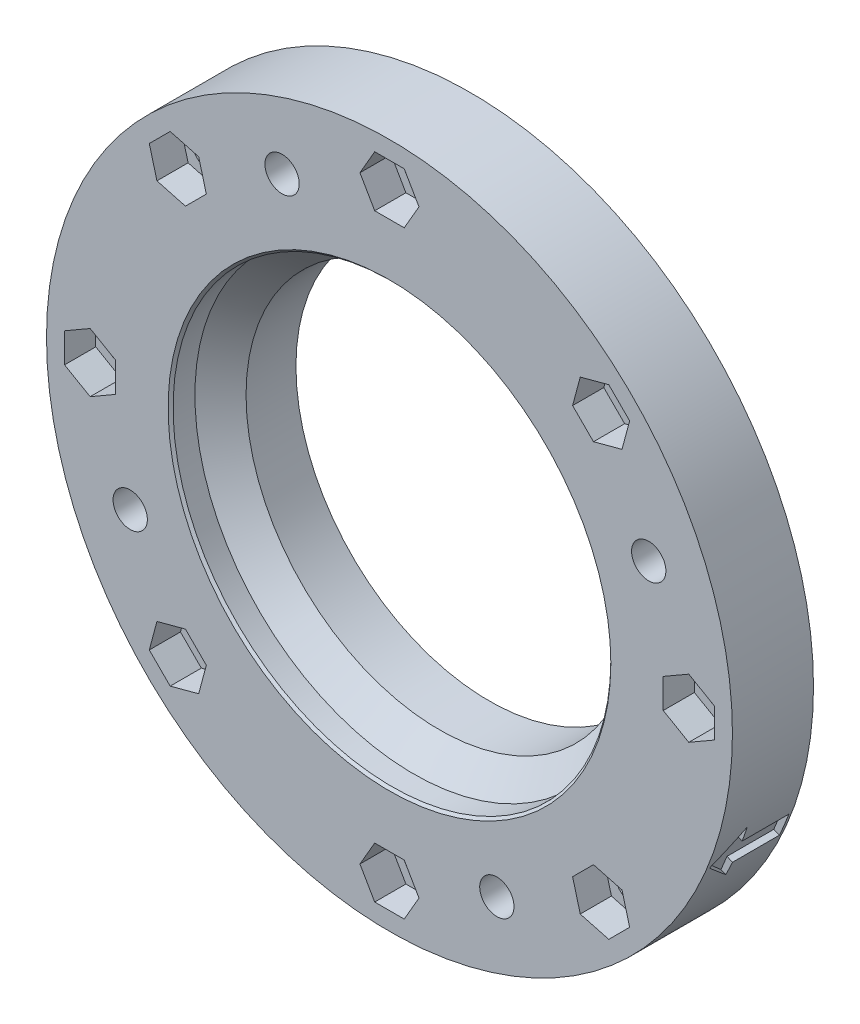
SolidWorks part; units mm, degrees
ref_plane "Piano frontale" through (0, 0, 0) normal (0, 0, 1) x (1, 0, 0)
ref_plane "Piano superiore" through (0, 0, 0) normal (0, 1, 0) x (1, 0, 0)
ref_plane "Piano destro" through (0, 0, 0) normal (1, 0, 0) x (0, 0, -1)
sketch "Schizzo1" plane through (0, 0, 0) normal (0, 0, 1) x (1, 0, 0)
  circle A0 centre (0, 0) radius 34
  circle A1 centre (0, 0) radius 55
  dimension "D1" = 110
  dimension "D2" = 68
extrude "Estrusione-Estrusione1" add sketch "Schizzo1" along normal blind 13
sketch "Schizzo2" plane through (0, 0, 13) normal (0, 0, 1) x (1, 0, 0)
  circle A0 centre (0, 0) radius 34
  circle A2 centre (0, 0) radius 34 construction
extrude "Estrusione-Estrusione2" add sketch "Schizzo2" against normal blind 8
sketch "Schizzo3" plane through (0, 0, 13) normal (0, 0, 1) x (1, 0, 0)
  circle A0 centre (0, 0) radius 48 construction
  circle A1 centre (0, 48) radius 2.75
  dimension "D1" = 96
  dimension "D2" = 5.5
extrude "Taglio-Estrusione1" cut sketch "Schizzo3" against normal through all
pattern_circular "RipetizioneCircolare1" count 8 over 360 about axis through (0, 0, 13) along (0, 0, -1) of "Taglio-Estrusione1"
sketch "Schizzo6" plane through (0, 0, 13) normal (0, 0, 1) x (1, 0, 0)
  line L1 (4.7343, 48) -> (2.3671, 52.1)
  line L2 (2.3671, 52.1) -> (-2.3671, 52.1)
  line L3 (-2.3671, 52.1) -> (-4.7343, 48)
  line L4 (-4.7343, 48) -> (-2.3671, 43.9)
  line L5 (-2.3671, 43.9) -> (2.3671, 43.9)
  line L6 (2.3671, 43.9) -> (4.7343, 48)
  circle A0 centre (0, 48) radius 4.1 construction
  dimension "D1" = 8.2
extrude "Taglio-Estrusione3" cut sketch "Schizzo6" against normal blind 5
pattern_circular "RipetizioneCircolare2" count 8 over 360 about axis through (0, 0, 13) along (0, 0, -1) of "Taglio-Estrusione3"
sketch "Schizzo7" plane through (0, 0, 13) normal (0, 0, 1) x (1, 0, 0)
  circle A0 centre (0, 0) radius 35
  dimension "D1" = 70
extrude "Taglio-Estrusione4" cut sketch "Schizzo7" against normal blind 8
sketch "Schizzo8" plane through (0, 0, 13) normal (0, 0, 1) x (1, 0, 0)
  line L0 (0, 48) -> (0, -43.9) construction
  line L1 (41.5746, 17.2208) -> (17.2208, -41.5746) construction
  line L2 (41.5746, 17.2208) -> (-17.2208, 41.5746) construction
  line L3 (-17.2208, 41.5746) -> (-41.5746, -17.2208) construction
  line L4 (17.2208, -41.5746) -> (-41.5746, -17.2208) construction
  line L5 (41.5746, 17.2208) -> (-41.5746, -17.2208) construction
  line L6 (-17.2208, 41.5746) -> (17.2208, -41.5746) construction
  line L7 (2.3671, -43.9) -> (-2.3671, -43.9) construction
  circle A0 centre (0, 0) radius 45 construction
  circle A1 centre (-17.2208, 41.5746) radius 2.75
  circle A2 centre (41.5746, 17.2208) radius 2.75
  circle A3 centre (17.2208, -41.5746) radius 2.75
  circle A4 centre (-41.5746, -17.2208) radius 2.75
  dimension "D1" = 90
  dimension "D3" = 5.5
  dimension "D2" = 22.5
extrude "Taglio-Estrusione5" cut sketch "Schizzo8" against normal through all
sketch "Schizzo9" plane through (0, 0, 0) normal (0, 0, -1) x (-1, 0, 0)
  line L1 (19.5879, 45.6746) -> (14.8536, 45.6746)
  line L2 (14.8536, 45.6746) -> (12.4865, 41.5746)
  line L3 (12.4865, 41.5746) -> (14.8536, 37.4746)
  line L4 (14.8536, 37.4746) -> (19.5879, 37.4746)
  line L5 (19.5879, 37.4746) -> (21.955, 41.5746)
  line L6 (21.955, 41.5746) -> (19.5879, 45.6746)
  circle A0 centre (17.2208, 41.5746) radius 4.1 construction
  dimension "D1" = 8.2
extrude "Taglio-Estrusione6" cut sketch "Schizzo9" against normal blind 5
pattern_circular "RipetizioneCircolare3" count 4 over 360 about axis through (0, 0, 13) along (0, 0, -1) of "Taglio-Estrusione6"
sketch "Schizzo10" plane through (0, 0, 0) normal (0, 0, -1) x (-1, 0, 0)
  circle A0 centre (0, 0) radius 34
  circle A1 centre (0, 0) radius 31
  circle A5 centre (0, 0) radius 34 construction
  dimension "D1" = 3
extrude "Estrusione-Estrusione3" add sketch "Schizzo10" along normal blind 3 and the other way blind 5
chamfer "Smusso1" distance 4 angle 45 1 edges at (35, 0, 5)
chamfer "Smusso2" distance 0.5 angle 45 2 edges at (-34, 0, -3) (35, 0, 13)
other "Sposta faccia1" flip direction yes face at (-34, 0, -2.5) offset 0.1 parameters "D1"=0.1
other "Sposta faccia2" flip direction yes face at (35, 0, 12.5) offset 0.1 parameters "D1"=0.1
ref_plane "Piano1" through (50.8134, -21.0476, 0) normal (0.9239, -0.3827, 0) x (0, 0, -1)
sketch "Schizzo11" plane through (50.8134, -21.0476, 0) normal (0.9239, -0.3827, 0) x (0, 0, -1)
  line L0 (-0.5, 0) -> (-0.5, 2)
  line L2 (-0.5, 2) -> (-8, 2)
  line L3 (-8, 2) -> (-8, 4.5)
  line L4 (-8, 4.5) -> (-12.5, 0)
  line L5 (-12.5, 0) -> (-8, -4.5)
  line L6 (-8, -4.5) -> (-8, -2)
  line L7 (-8, -2) -> (-0.5, -2)
  line L9 (-0.5, -2) -> (-0.5, 0)
  line L10 (0, -55) -> (0, 55) construction
  dimension "D1" = 4
  dimension "D2" = 12
  dimension "D3" = 0.5
  dimension "D4" = 2.5
extrude "Taglio-Estrusione7" cut sketch "Schizzo11" against normal blind 1
